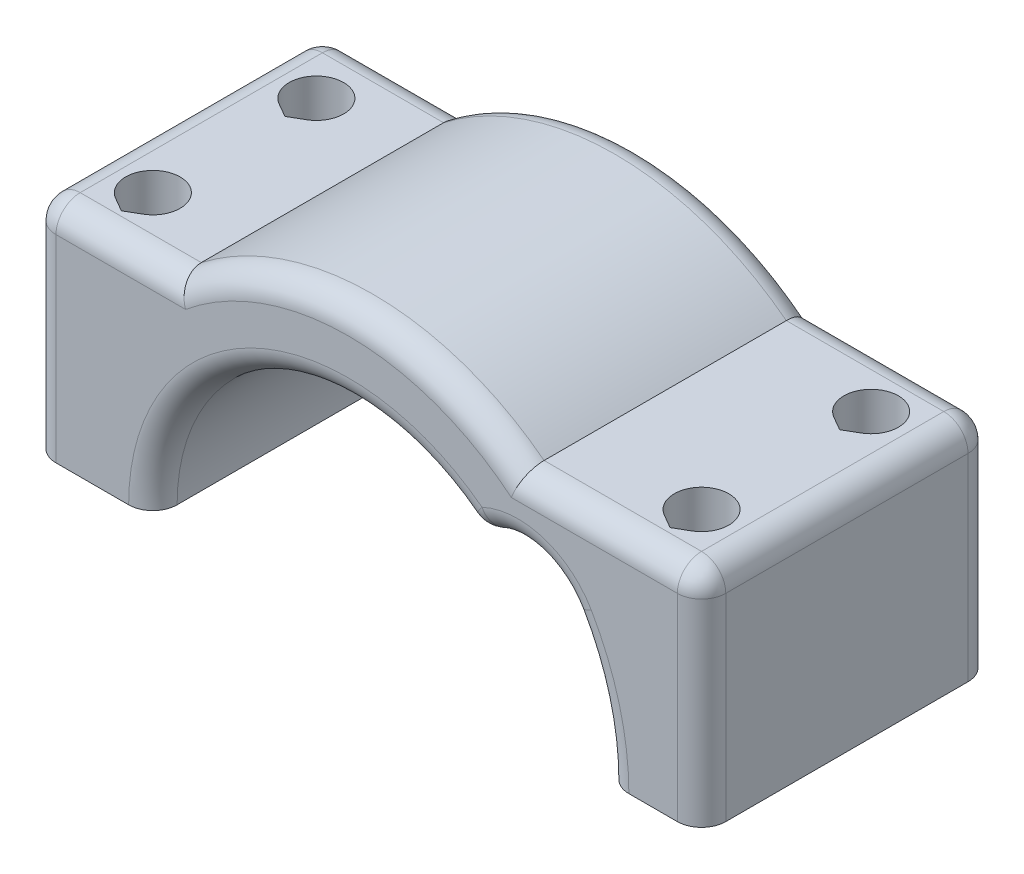
SolidWorks part; units mm, degrees
ref_plane "Ebene vorne" through (0, 0, 0) normal (0, 0, 1) x (1, 0, 0)
ref_plane "Ebene oben" through (0, 0, 0) normal (0, 1, 0) x (1, 0, 0)
ref_plane "Ebene rechts" through (0, 0, 0) normal (1, 0, 0) x (0, 0, -1)
sketch "Skizze1" plane through (0, 0, 0) normal (0, 0, 1) x (1, 0, 0)
  line L0 (16.15, 0) -> (29.15, 0)
  line L1 (29.15, 0) -> (29.15, 18.3221)
  line L2 (29.15, 18.3221) -> (14.15, 18.3221)
  line L3 (-16.15, 0) -> (-26.15, 0)
  line L4 (-26.15, 0) -> (-26.15, 18.3221)
  line L5 (-26.15, 18.3221) -> (-14.15, 18.3221)
  line L6 (18.3164, 10.575) -> (0, 0) construction
  circle A0 centre (0, 0) radius 16.15
  arc A1 (14.15, 18.3221) -> (-14.15, 18.3221) centre (0, 0) ccw
  arc A2 (21.15, 0) -> (18.3164, 10.575) centre (0, 0) ccw
  arc A3 (18.3164, 10.575) -> (10.8461, 11.9659) centre (13.9863, 8.075) ccw
  point P16 (11.5265, 14.7557)
  point P17 (0, 0)
  point P18 (0, 0)
  dimension "D1" = 32.3
  dimension "D6" = 7
  dimension "D8" = 5
  dimension "D2" = 13
  dimension "D3" = 12
  dimension "D4" = 10
  dimension "D7" = 30
extrude "Aufsatz-Linear austragen1" add sketch "Skizze1" along normal mid plane 24 contours L2 A1 L5 L4 L3 A0 L0 L1 region at (21.0084, 5.6292, 0)
sketch "Skizze2" plane through (0, 18.3221, 0) normal (0, 1, 0) x (1, 0, 0)
  line L0 (29.15, -12) -> (29.15, 12) construction
  line L1 (29.15, 12) -> (14.15, 12) construction
  line L2 (24.15, 7) -> (24.15, 4.4019) construction
  line L3 (24.15, 4.4019) -> (25.275, 5.0514)
  line L4 (24.15, 4.4019) -> (23.025, 5.0514)
  line L5 (-26.15, 12) -> (-14.15, 12) construction
  line L6 (-26.15, -12) -> (-26.15, 12) construction
  line L7 (-21.15, 6.5) -> (-21.15, 3.9019) construction
  line L8 (-21.15, 3.9019) -> (-20.025, 4.5514)
  line L9 (-21.15, 3.9019) -> (-22.275, 4.5514)
  line L10 (29.15, -12) -> (14.15, -12) construction
  line L11 (24.15, -7) -> (24.15, -9.5981)
  line L12 (24.15, -9.5981) -> (25.275, -8.9486)
  line L13 (24.15, -9.5981) -> (23.025, -8.9486)
  line L14 (-26.15, -12) -> (-14.15, -12) construction
  line L15 (-21.15, -7) -> (-21.15, -9.5981) construction
  line L16 (-21.15, -9.5981) -> (-20.025, -8.9486)
  line L17 (-21.15, -9.5981) -> (-22.275, -8.9486)
  circle A0 centre (24.15, 7) radius 2.25
  circle A1 centre (-21.15, 6.5) radius 2.25
  circle A2 centre (24.15, -7) radius 2.25
  circle A3 centre (-21.15, -7) radius 2.25
  dimension "D1" = 4.5
  dimension "D6" = 4.5
  dimension "D9" = 4.5
  dimension "D13" = 4.5
  dimension "D2" = 5
  dimension "D3" = 5
  dimension "D4" = 60
  dimension "D5" = 5.5
  dimension "D7" = 5
  dimension "D8" = 60
  dimension "D10" = 5
  dimension "D11" = 5
  dimension "D12" = 60
  dimension "D14" = 5
  dimension "D15" = 5
  dimension "D16" = 60
extrude "Schnitt-Linear austragen1" cut sketch "Skizze2" against normal through all contours A1 | A1 L9 L8 | A1 region at (-21.15, 18.3221, -4.1745) region at (-21.15, 18.3221, -6.5)
extrude "Schnitt-Linear austragen2" cut sketch "Skizze2<4>" against normal through all contours A0 | A0 L4 L3 region at (24.15, 18.3221, -4.6745) region at (24.15, 18.3221, -7)
sketch "Skizze2<4>" plane through (0, 18.3221, 0) normal (0, 1, 0) x (1, 0, 0) same geometry as "Skizze2"
extrude "Schnitt-Linear austragen3" cut sketch "Skizze2<5>" against normal through all contours A2 | A2 L13 L11 | A2 L11 L12 | A3 | A3 L17 L16 region at (24.4392, 18.3221, 9.3255) region at (23.8608, 18.3221, 9.3255) region at (23.5841, 18.3221, 9.1119) region at (-21.15, 18.3221, 9.3255) region at (-21.15, 18.3221, 7)
sketch "Skizze2<5>" plane through (0, 18.3221, 0) normal (0, 1, 0) x (1, 0, 0) same geometry as "Skizze2"
fillet "Verrundung1" radius 2 11 edges at (20.4293, 5.474, 12) (20.4293, 5.474, -12) (10.8461, 11.9659, 0) (14.9016, 12.9905, 12) (14.9016, 12.9905, -12) (29.15, 9.1611, -12) (29.15, 9.1611, 12) (-26.15, 9.1611, -12) (-26.15, 9.1611, 12) (-6.5444, 14.7646, -12) (-6.5444, 14.7646, 12)
fillet "Verrundung2" radius 2 12 edges at (20.65, 18.3221, 12) (28.5642, 18.3221, 11.4142) (20.65, 18.3221, -12) (28.5642, 18.3221, -11.4142) (-19.15, 18.3221, 12) (-25.5642, 18.3221, 11.4142) (-19.15, 18.3221, -12) (-25.5642, 18.3221, -11.4142) (0, 23.15, -12) (0, 23.15, 12) (29.15, 18.3221, 0) (-26.15, 18.3221, 0)
